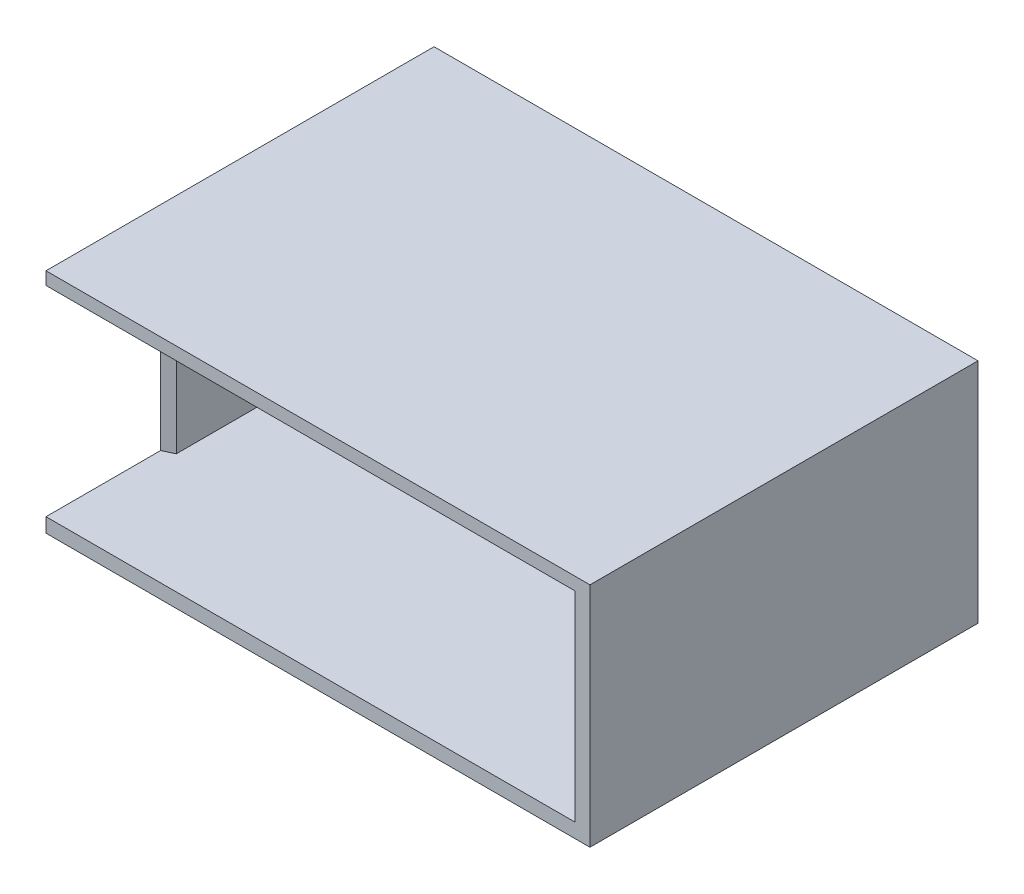
SolidWorks part; units mm, degrees
material "Custom Plastic"
ref_plane "Front Plane" through (0, 0, 0) normal (0, 0, 1) x (1, 0, 0)
ref_plane "Top Plane" through (0, 0, 0) normal (0, 1, 0) x (1, 0, 0)
ref_plane "Right Plane" through (0, 0, 0) normal (1, 0, 0) x (0, 0, -1)
sketch "Sketch1" plane through (0, 0, 0) normal (0, 0, 1) x (1, 0, 0)
  line L1 (0, 15) -> (145, 15)
  line L2 (0, 15) -> (0, -15)
  line L3 (0, -15) -> (145, -15)
  line L4 (145, 15) -> (145, -15)
  circle A0 centre (0, 0) radius 27.5
  circle A1 centre (145, 0) radius 27.5
  circle A2 centre (0, 0) radius 20
  point P9 (0, 0)
  dimension "D1" = 55
  dimension "D4" = 55
  dimension "D5" = 40
  dimension "D2" = 145
  dimension "D3" = 30
extrude "Boss-Extrude1" add sketch "Sketch1" along normal blind 25 contours L3 A1 L1 L4 | A1 L1 A0 L3 | L1 A1 L3 L4 | A2 L3 A0 L1 | A2 L1 A0 L3 | L3 A2 L1 L2 | L1 A2 L3 L2 region at (-6.7804, 0, 0) region at (9.0671, 0, 0) region at (-20.747, 0, 0) region at (21.8665, 0, 0) region at (72.5, 0, 0) region at (151.4116, 0, 0) region at (131.9332, 0, 0)
sketch "Sketch16" plane through (0, 0, 0) normal (0, 0, -1) x (-1, 0, 0)
  line L0 (-121.9511, -15) -> (-133.5193, -6.45) construction
  line L1 (-133.5193, -6.45) -> (-166.9193, -6.45)
  line L2 (-133.5193, -6.45) -> (-133.5193, 6.45)
  line L3 (-133.5193, 6.45) -> (-166.9193, 6.45)
  line L4 (-166.9193, -6.45) -> (-166.9193, 6.45)
  line L5 (-23.0489, -15) -> (-121.9511, -15) construction
  line L7 (-133.5193, 6.45) -> (-121.9511, 15) construction
  arc A1 (-121.9511, 15) -> (-121.9511, -15) centre (-145, 0) ccw construction
  dimension "D1" = 11.5682
  dimension "D2" = 33.4
  dimension "D3" = 12.9
extrude "Cut-Extrude10" cut sketch "Sketch16" against normal blind 4.5
ref_plane "Plane1" through (0, 0, 0) normal (0, -1, 0) x (-1, 0, 0)
sketch "Sketch19" plane through (0, 0, 0) normal (0, 0, -1) x (-1, 0, 0)
  circle A0 centre (0, 0) radius 20
extrude "Cut-Extrude14" cut sketch "Sketch19" against normal blind 7.55 contours A0
ref_plane "Plane2" through (0, 0, 6.5) normal (0, 0, -1) x (-1, 0, 0)
sketch "Sketch17" plane through (0, 0, 0) normal (0, 0, -1) x (-1, 0, 0)
  line L1 (-162.0193, 6.45) -> (-138.4193, 6.45)
  line L2 (-162.0193, 6.45) -> (-162.0193, -6.45)
  line L3 (-162.0193, -6.45) -> (-138.4193, -6.45)
  line L4 (-133.5193, -6.45) -> (-133.5193, 6.45)
  line L5 (-133.5193, 6.45) -> (-166.9193, 6.45)
  line L7 (-166.9193, -6.45) -> (-133.5193, -6.45)
  line L8 (-133.5193, -6.45) -> (-133.5193, 6.45)
  line L9 (-133.5193, 6.45) -> (-166.9193, 6.45)
  line L11 (-166.9193, -6.45) -> (-133.5193, -6.45)
  line L12 (-138.4193, 6.45) -> (-138.4193, -6.45)
  line L15 (-166.9193, 6.45) -> (-166.9193, -6.45)
  line L17 (-166.9193, 6.45) -> (-166.9193, -6.45)
  line M9 (-166.9193, 6.45) -> (-133.5193, 6.45)
  line M11 (-133.5193, -6.45) -> (-166.9193, -6.45)
  dimension "D2" = 4.9
  dimension "D3" = 4.9
  dimension "D1" = 0
extrude "Cut-Extrude11" cut sketch "Sketch17" against normal through all contours L12 L2 M9 M11 region at (150.2193, 0, 0)
sketch "Sketch18" plane through (0, 0, 0) normal (0, -1, 0) x (-1, 0, 0)
  line L0 (-138.4193, -25) -> (-138.4193, -15)
  line L6 (-122.4193, -25) -> (-122.4193, -22.5)
  line L8 (-166.9193, -4.5) -> (-162.0193, -4.5)
  line L9 (-166.9193, 0) -> (-166.9193, -4.5)
  line L11 (-166.9193, 0) -> (-166.9193, -4.5)
  line L13 (-133.5193, -4.5) -> (-133.5193, 0)
  line L14 (-133.5193, 0) -> (-166.9193, 0)
  line L16 (-166.9193, -4.5) -> (-162.0193, -4.5)
  line L21 (-133.5193, -4.5) -> (-133.5193, 0)
  line L22 (-133.5193, 0) -> (-166.9193, 0)
  line L26 (-122.4193, -22.5) -> (-138.4193, -15)
  line L28 (-23.0489, -25) -> (-121.9511, -25) construction
  line L30 (-138.4193, -25) -> (-122.4193, -25)
  line L31 (-138.4193, -15) -> (-138.4193, -25)
  line L34 (-162.0193, -25) -> (-138.4193, -25)
  line L35 (-162.0193, -25) -> (-138.4193, -25)
  line L36 (-138.4193, -25) -> (-138.4193, -4.5)
  line L37 (-138.4193, -25) -> (-138.4193, -4.5)
  line L38 (-162.0193, -4.5) -> (-162.0193, -25)
  line L40 (-162.0193, -4.5) -> (-162.0193, -25)
  line L42 (-138.4193, -4.5) -> (-133.5193, -4.5)
  line L43 (-138.4193, -4.5) -> (-133.5193, -4.5)
  dimension "D2" = 15
  dimension "D3" = 16
  dimension "D4" = 2.5
  dimension "D1" = 0
extrude "Cut-Extrude13" cut sketch "Sketch18" against normal mid plane 12.9 contours L0 region at (132.0193, 0, 21.5)
sketch "Sketch20" plane through (0, 0, 6.5) normal (0, 0, -1) x (-1, 0, 0)
  line L0 (-133.5193, 6.45) -> (-166.9193, 6.45) construction
  line L1 (-166.9193, 6.45) -> (-133.5193, 6.45)
  line L2 (-166.9193, 6.45) -> (-166.9193, -6.45)
  line L3 (-166.9193, -6.45) -> (-133.5193, -6.45)
  line L4 (-133.5193, 6.45) -> (-133.5193, -6.45)
  line L5 (-166.9193, 6.45) -> (-166.9193, -6.45) construction
  line L6 (-166.9193, -6.45) -> (-133.5193, -6.45) construction
  dimension "D1" = 33.4
extrude "Cut-Extrude15" cut sketch "Sketch20" against normal through all
sketch "Sketch21" plane through (0, 0, 0) normal (0, 0, -1) x (-1, 0, 0)
  circle A0 centre (-136.75, 0) radius 1.1
  circle A1 centre (-163.75, 0) radius 1.1
  dimension "D3" = 2.2
  dimension "D1" = 14.7989
  dimension "D2" = 27
extrude "Cut-Extrude16" cut sketch "Sketch21" against normal through all contours A1 | A0 region at (136.75, 0, 0) region at (163.75, 0, 0)
ref_axis "Axis1" through (136.75, 0, 34.2314) along (0, 0, -1)
sketch "Sketch22" plane through (0, 0, 25) normal (0, 0, 1) x (1, 0, 0)
  circle A0 centre (0, 0) radius 2
  arc A4 (23.0489, 15) -> (23.0489, -15) centre (0, 0) ccw construction
  dimension "D1" = 4
extrude "Cut-Extrude17" cut sketch "Sketch22" against normal up to surface (17.45 mm away) up to face at (-20, 0, 7.55)
sketch "Sketch23" plane through (0, 0, 0) normal (0, 0, -1) x (-1, 0, 0)
  line L1 (29.7321, -41.7179) -> (-132.8303, -41.7179)
  line L2 (29.7321, -41.7179) -> (29.7321, 44.859)
  line L3 (29.7321, 44.859) -> (-132.8303, 44.859)
  line L4 (-132.8303, -41.7179) -> (-132.8303, 44.859)
extrude "Cut-Extrude18" cut sketch "Sketch23" against normal through all
sketch "Sketch24" plane through (0, 0, 0) normal (0, 0, -1) x (-1, 0, 0)
  line L1 (-172.0883, -7.372) -> (-125.7826, -7.372)
  line L2 (-172.0883, -7.372) -> (-172.0883, -32.6339)
  line L3 (-172.0883, -32.6339) -> (-125.7826, -32.6339)
  line L4 (-125.7826, -7.372) -> (-125.7826, -32.6339)
  line L5 (-122.132, 7.2722) -> (-172.3145, 7.2722)
  line L6 (-122.132, 7.2722) -> (-122.132, 27.7288)
  line L7 (-122.132, 27.7288) -> (-172.3145, 27.7288)
  line L8 (-172.3145, 7.2722) -> (-172.3145, 27.7288)
  line L9 (-185.4625, 7.2722) -> (-167.7869, 7.2722)
  line L10 (-185.4625, 7.2722) -> (-185.4625, -7.372)
  line L11 (-185.4625, -7.372) -> (-167.7869, -7.372)
  line L12 (-167.7869, 7.2722) -> (-167.7869, -7.372)
  arc M17 (-132.8303, 24.6607) -> (-132.8303, -24.6607) centre (-145, 0) ccw
  line M18 (-132.8303, -24.6607) -> (-132.8303, 24.6607)
extrude "Cut-Extrude19" cut sketch "Sketch24" against normal through all contours L1 M17 M18 | L10 L11 L1 L5 L9 M17 | L5 M18 M17 region at (178.8137, -0.0524, 0) region at (149.5018, -16.2094, 0) region at (149.5181, 16.1551, 0)
sketch "Sketch26" plane through (0, 0, 0) normal (0, 0, -1) x (-1, 0, 0)
  line L1 (-174.3172, 9.9292) -> (-167.877, 9.9292)
  line L2 (-174.3172, 9.9292) -> (-174.3172, -11.1252)
  line L3 (-174.3172, -11.1252) -> (-167.877, -11.1252)
  line L4 (-167.877, 9.9292) -> (-167.877, -11.1252)
extrude "Cut-Extrude20" cut sketch "Sketch26" against normal through all
